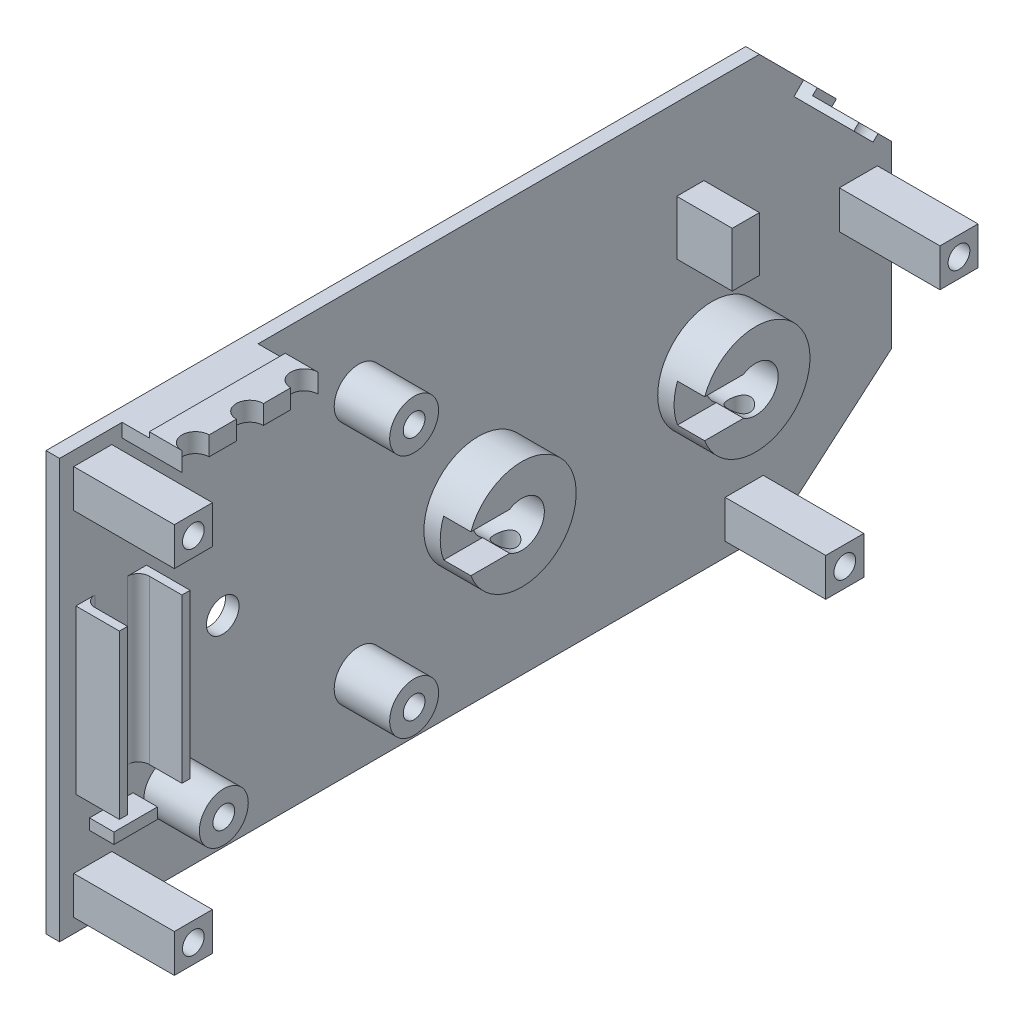
SolidWorks part; units mm, degrees
note: '?' marks a value the reader was unsure of.
ref_plane "Front Plane" through (0, 0, 0) normal (0, 0, 1) x (1, 0, 0)
ref_plane "Top Plane" through (0, 0, 0) normal (0, 1, 0) x (1, 0, 0)
ref_plane "Right Plane" through (0, 0, 0) normal (1, 0, 0) x (0, 0, -1)
sketch "Sketch1" plane through (0, 0, 0) normal (1, 0, 0) x (0, 0, -1)
  line L0 (0, 0) -> (0, 77)
  line L1 (0, 77) -> (127, 77)
  line L2 (127, 77) -> (153, 51)
  line L3 (153, 51) -> (153, 18)
  line L4 (153, 18) -> (132, 0)
  line L5 (132, 0) -> (0, 0)
  dimension "D1" = 132
  dimension "D2" = 77
  dimension "D3" = 26
  dimension "D4" = 26
  dimension "D5" = 153
  dimension "D6" = 18
extrude "Base" add sketch "Sketch1" along normal blind 2.5
ref_plane "Middle" through (13.5, 0, 0) normal (1, 0, 0) x (0, 0, -1)
sketch "Sketch2" plane through (2.5, 0, 0) normal (1, 0, 0) x (0, 0, -1)
  line L1 (113.5, 62) -> (118.5, 62)
  line L2 (113.5, 62) -> (113.5, 52)
  line L3 (113.5, 52) -> (118.5, 52)
  line L4 (118.5, 62) -> (118.5, 52)
  line L5 (113.5, 62) -> (118.5, 52) construction
  line L6 (113.5, 52) -> (118.5, 62) construction
  circle A0 centre (20, 15) radius 4.5
  circle A1 centre (55, 15) radius 4.5
  circle A2 centre (55, 60) radius 4.5
  circle A3 centre (20, 15) radius 2
  circle A4 centre (55, 15) radius 2
  circle A5 centre (55, 60) radius 2
  point P9 (116, 57)
  dimension "D1" = 9
  dimension "D2" = 4
  dimension "D3" = 20
  dimension "D4" = 15
  dimension "D5" = 55
  dimension "D6" = 60
  dimension "D7" = 55
  dimension "D8" = 116
  dimension "D9" = 57
  dimension "D10" = 10
  dimension "D11" = 5
extrude "PCB_Mount" add sketch "Sketch2" along normal blind 10.2
sketch "Sketch24" plane through (12.7, 0, 0) normal (1, 0, 0) x (0, 0, -1)
  circle A0 centre (55, 60) radius 2 construction
  circle A1 centre (55, 15) radius 2 construction
  circle A2 centre (20, 15) radius 2 construction
  circle A3 centre (55, 60) radius 2
  circle A4 centre (55, 15) radius 2
  circle A5 centre (20, 15) radius 2
extrude "Boss-Extrude14" add sketch "Sketch24" against normal up to next from offset 4.5
ref_plane "Plane1" through (0, 32, 0) normal (0, 1, 0) x (1, 0, 0)
sketch "Sketch3" plane through (2.5, 0, 0) normal (1, 0, 0) x (0, 0, -1)
  line L0 (5.775, 32) -> (-5.775, 32) construction
  circle A0 centre (77, 32) radius 4.15
  circle A1 centre (120, 32) radius 4.15
  circle A2 centre (77, 32) radius 10
  circle A3 centre (120, 32) radius 10
  dimension "D3" = 8.3
  dimension "D4" = 20
  dimension "D1" = 77
  dimension "D2" = 120
extrude "Boss-Extrude3" add sketch "Sketch3" along normal blind 8
sketch "Sketch4" plane through (10.5, 0, 0) normal (1, 0, 0) x (0, 0, -1)
  line L1 (74.7701, 35.5) -> (67, 35.5)
  line L2 (74.7701, 35.5) -> (74.7701, 28.5)
  line L3 (74.7701, 28.5) -> (67, 28.5)
  line L4 (67, 35.5) -> (67, 28.5)
  line L5 (117.7701, 35.5) -> (110, 35.5)
  line L6 (117.7701, 35.5) -> (117.7701, 28.5)
  line L7 (117.7701, 28.5) -> (110, 28.5)
  line L8 (110, 35.5) -> (110, 28.5)
  circle A0 centre (77, 32) radius 4.15 construction
  circle A1 centre (77, 32) radius 10 construction
  circle A2 centre (120, 32) radius 4.15 construction
  circle A3 centre (120, 32) radius 10 construction
  dimension "D1" = 7
extrude "Cut-Extrude1" cut sketch "Sketch4" against normal blind 5
ref_axis "Axis1" through (10.5, 32, -77) along (-1, 0, 0)?
ref_axis "Axis2" through (10.5, 32, -120) along (-1, 0, 0)?
sketch "Sketch5" plane through (0, 32, 0) normal (0, 1, 0) x (1, 0, 0)
  line L2 (10.5, 77) -> (2.5, 77) construction
  line L3 (10.5, 120) -> (2.5, 120) construction
  line L4 (10.5, 67.6325) -> (10.5, 87) construction
  circle A0 centre (7.5, 77) radius 2
  circle A1 centre (7.5, 120) radius 2
  dimension "D1" = 4
  dimension "D2" = 3
extrude "Cut-Extrude2" cut sketch "Sketch5" against normal through all
sketch "Sketch13" plane through (0, 77, 0) normal (0, 1, 0) x (1, 0, 0)
  line L1 (13.5, 11.5) -> (2.5, 11.5)
  line L2 (13.5, 11.5) -> (13.5, 36.5)
  line L3 (13.5, 36.5) -> (2.5, 36.5)
  line L4 (2.5, 11.5) -> (2.5, 36.5)
  line L5 (13.5, 11.5) -> (2.5, 36.5) construction
  line L6 (13.5, 36.5) -> (2.5, 11.5) construction
  line L7 (2.5, 127) -> (2.5, 0) construction
  line L8 (13.5, -42.35) -> (13.5, 42.35) construction
  point P0 (8, 24)
  dimension "D1" = 24
  dimension "D2" = 25
extrude "Boss-Extrude8" add sketch "Sketch13" against normal blind 2.5
sketch "Sketch15" plane through (0, 77, 0) normal (0, 1, 0) x (1, 0, 0)
  line L0 (13.5, 11.5) -> (13.5, 36.5) construction
  line L1 (13.5, 11.5) -> (7.5, 11.5)
  line L2 (13.5, 11.5) -> (13.5, 36.5)
  line L3 (13.5, 36.5) -> (7.5, 36.5)
  line L4 (7.5, 11.5) -> (7.5, 36.5)
  point P6 (13.5, 24)
  point P7 (13.5, 24)
  dimension "D1" = 6
  dimension "D2" = 25
extrude "Boss-Extrude9" add sketch "Sketch15" along normal blind 1 and the other way blind 2.5
sketch "Sketch16" plane through (0, 78, 0) normal (0, 1, 0) x (1, 0, 0)
  line L0 (13.5, 11.5) -> (13.5, 36.5) construction
  circle A0 centre (13.5, 24) radius 2.5
  circle A1 centre (13.5, 34) radius 2.5
  circle A2 centre (13.5, 14) radius 2.5
  dimension "D3" = 5
  dimension "D1" = 10
  dimension "D2" = 10
extrude "Cut-Extrude4" cut sketch "Sketch16" against normal up to next
sketch "Sketch9" plane through (0, 0, 0) normal (-1, 0, 0) x (0, 0, 1)
  line L0 (-127, 77) -> (-128.6971, 77)
  line L1 (-128.6971, 77) -> (-140.3643, 65.3327)
  line L2 (-140.3643, 65.3327) -> (-139.5158, 64.4842)
  line L3 (-153, 51) -> (-127, 77) construction
  line L4 (-139.5158, 64.4842) -> (-127, 77)
  dimension "D1" = 1.2
  dimension "D2" = 16.5
extrude "Boss-Extrude5" add sketch "Sketch9" against normal up to vertex
sketch "Sketch10" plane through (2.5, 0, 0) normal (1, 0, 0) x (0, 0, -1)
  line L0 (140.3643, 65.3327) -> (136.8288, 68.8683)
  line L1 (140.3643, 65.3327) -> (138.5966, 63.565)
  line L2 (136.8288, 68.8683) -> (135.061, 67.1005)
  line L3 (138.5966, 63.565) -> (135.061, 67.1005)
  line L4 (128.6971, 77) -> (140.3643, 65.3327) construction
  dimension "D1" = 2.5
  dimension "D2" = 5
extrude "Boss-Extrude6" add sketch "Sketch10" along normal blind 2.5
sketch "Sketch12" plane through (0, 101.0808, -101.0808) normal (0, -0.7071, 0.7071) x (1, 0, 0)
  line L0 (5, -48.0553) -> (5, -53.0553)
  line L1 (5, -48.0553) -> (13.5, -48.0553)
  line L2 (5, -53.0553) -> (13.5, -53.0553)
  line L4 (0, -72.1249) -> (0, -53.0553) construction
  arc A0 (13.5, -48.0553) -> (13.5, -53.0553) centre (13.5, -50.5553) ccw
  dimension "D1" = 2.5
  dimension "D2" = 13.5
extrude "Boss-Extrude7" add sketch "Sketch12" against normal blind 1.3
sketch "Sketch19" plane through (2.5, 0, 0) normal (1, 0, 0) x (0, 0, -1)
  line L0 (0, 77) -> (0, 0) construction
  line L1 (3, 52) -> (4.5, 52)
  line L2 (3, 52) -> (3, 22)
  line L3 (3, 22) -> (4.5, 22)
  line L4 (4.5, 52) -> (4.5, 22)
  line L6 (14.5, 52) -> (16, 52)
  line L7 (14.5, 52) -> (14.5, 22)
  line L8 (14.5, 22) -> (16, 22)
  line L9 (16, 52) -> (16, 22)
  dimension "D1" = 3
  dimension "D2" = 1.5
  dimension "D3" = 22
  dimension "D4" = 30
  dimension "D5" = 10
extrude "Boss-Extrude11" add sketch "Sketch19" along normal blind 8
fillet "Fillet1" radius 2 2 edges at (2.5, 37, -4.5) (2.5, 37, -14.5)
sketch "Sketch20" plane through (2.5, 0, 0) normal (1, 0, 0) x (0, 0, -1)
  line L0 (3, 22) -> (16, 22) construction
  line L3 (5.5, 15) -> (13.5, 15)
  line L4 (5.5, 15) -> (5.5, 17)
  line L5 (5.5, 17) -> (13.5, 17)
  line L6 (13.5, 15) -> (13.5, 17)
  line L7 (5.5, 15) -> (13.5, 17) construction
  line L8 (5.5, 17) -> (13.5, 15) construction
  point P5 (9.5, 16)
  point P10 (9.5, 22)
  dimension "D1" = 15
  dimension "D2" = 2
  dimension "D3" = 8
extrude "Boss-Extrude12" add sketch "Sketch20" along normal blind 4.5
sketch "Sketch21" plane through (2.5, 0, 0) normal (1, 0, 0) x (0, 0, -1)
  line L0 (11.5, 77) -> (0, 77) construction
  line L1 (2.6, 74.4) -> (9.6, 74.4)
  line L2 (2.6, 74.4) -> (2.6, 67.4)
  line L3 (2.6, 67.4) -> (9.6, 67.4)
  line L4 (9.6, 74.4) -> (9.6, 67.4)
  line L5 (2.6, 2.6) -> (9.6, 2.6)
  line L6 (2.6, 2.6) -> (2.6, 9.6)
  line L7 (2.6, 9.6) -> (9.6, 9.6)
  line L8 (9.6, 2.6) -> (9.6, 9.6)
  line L9 (129.4, 2.6) -> (122.4, 2.6)
  line L10 (129.4, 2.6) -> (129.4, 9.6)
  line L11 (129.4, 9.6) -> (122.4, 9.6)
  line L12 (122.4, 2.6) -> (122.4, 9.6)
  line L13 (150.4, 48.4) -> (143.4, 48.4)
  line L14 (150.4, 48.4) -> (150.4, 41.4)
  line L15 (150.4, 41.4) -> (143.4, 41.4)
  line L16 (143.4, 48.4) -> (143.4, 41.4)
  line L17 (153, 18) -> (153, 51) construction
  dimension "D1" = 2.6
  dimension "D2" = 2.6
  dimension "D3" = 2.6
  dimension "D4" = 2.6
  dimension "D5" = 2.6
  dimension "D6" = 2.6
  dimension "D7" = 7
extrude "Boss-Extrude13" add sketch "Sketch21" along normal blind 18.5
sketch "Sketch22" plane through (21, 0, 0) normal (1, 0, 0) x (0, 0, -1)
  line L0 (2.6, 9.6) -> (9.6, 2.6) construction
  line L1 (122.4, 9.6) -> (129.4, 2.6) construction
  line L2 (143.4, 48.4) -> (150.4, 41.4) construction
  line L3 (2.6, 74.4) -> (9.6, 67.4) construction
  circle A0 centre (6.1, 6.1) radius 2
  circle A1 centre (6.1, 70.9) radius 2
  circle A2 centre (146.9, 44.9) radius 2
  circle A3 centre (125.9, 6.1) radius 2
  point P6 (6.1, 6.1)
  dimension "D1" = 4
extrude "Cut-Extrude5" cut sketch "Sketch22" against normal blind 4.5
sketch "Sketch25" plane through (0, 0, 0) normal (-1, 0, 0) x (0, 0, 1)
  circle A0 centre (-30, 37) radius 3
  dimension "D3" = 6
  dimension "D1" = 30
  dimension "D2" = 37
extrude "Cut-Extrude6" cut sketch "Sketch25" against normal up to next
equation "\"D2@Sketch16\"=\"D1@Sketch16\""
equation "\"D1@Sketch21\"=\"D2@Sketch21\""
equation "\"D3@Sketch21\"=\"D2@Sketch21\""
equation "\"D4@Sketch21\"=\"D2@Sketch21\""
equation "\"D5@Sketch21\"=\"D2@Sketch21\""
equation "\"D6@Sketch21\"=\"D2@Sketch21\""
